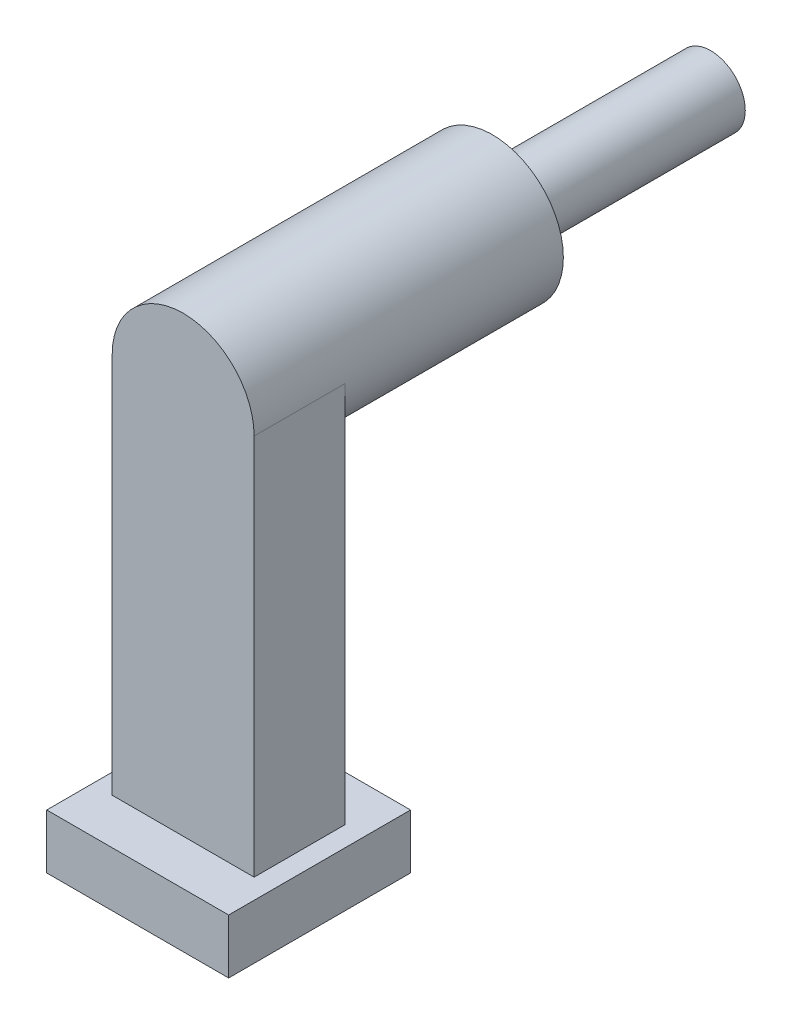
SolidWorks part; units mm, degrees
ref_plane "Front Plane" through (0, 0, 0) normal (0, 0, 1) x (1, 0, 0)
ref_plane "Top Plane" through (0, 0, 0) normal (0, 1, 0) x (1, 0, 0)
ref_plane "Right Plane" through (0, 0, 0) normal (1, 0, 0) x (0, 0, -1)
sketch "Sketch1" plane through (0, 0, 0) normal (0, 0, 1) x (1, 0, 0)
  circle A1 centre (0, 0) radius 1.9
  dimension "D2" = 3.8
extrude "Boss-Extrude1" add sketch "Sketch1" along normal blind 12 from offset 1
sketch "Sketch2" plane through (0, 0, 0) normal (0, 0, 1) x (1, 0, 0)
  circle A0 centre (0, 0) radius 3.9
  dimension "D1" = 7.8
extrude "Boss-Extrude2" add sketch "Sketch2" along normal blind 17 from offset 13
sketch "Sketch6" plane through (0, 0, 0) normal (0, 1, 0) x (1, 0, 0)
  line L0 (0, -30) -> (0, -25) construction
  line L1 (-3.9, -30) -> (3.9, -30) construction
  line L2 (-3.9, -13) -> (-3.9, -30) construction
  line L3 (-3.9, -25) -> (3.9, -25)
  line L4 (-3.9, -25) -> (-3.9, -30)
  line L5 (-3.9, -30) -> (3.9, -30)
  line L6 (3.9, -25) -> (3.9, -30)
  dimension "D1" = 5
extrude "Boss-Extrude3" add sketch "Sketch6" against normal blind 21
sketch "Sketch7" plane through (0, -21, 0) normal (0, -1, 0) x (1, 0, 0)
  line L0 (0, 30) -> (0, 25) construction
  line L1 (-3.9, 30) -> (3.9, 30) construction
  line L2 (-3.9, 25) -> (3.9, 25) construction
  line L3 (-3.9, 27.5) -> (3.9, 27.5) construction
  line L4 (-3.9, 25) -> (-3.9, 30) construction
  line L5 (3.9, 30) -> (3.9, 25) construction
  line L6 (5, 32.5) -> (-5, 32.5)
  line L7 (-5, 32.5) -> (-5, 22.5)
  line L10 (5, 22.5) -> (-5, 22.5)
  line L11 (5, 32.5) -> (5, 22.5)
  point P17 (-5, 27.5)
  point P18 (0, 32.5)
  point P19 (0, 22.5)
  dimension "D1" = 5
  dimension "D2" = 5
extrude "Boss-Extrude4" add sketch "Sketch7" along normal blind 3
sketch "Sketch8" plane through (0, 0, 1) normal (0, 0, -1) x (-1, 0, 0)
  line L0 (0, 5.9734) -> (0, -28.4513) construction
  point P0 (0, 0)
